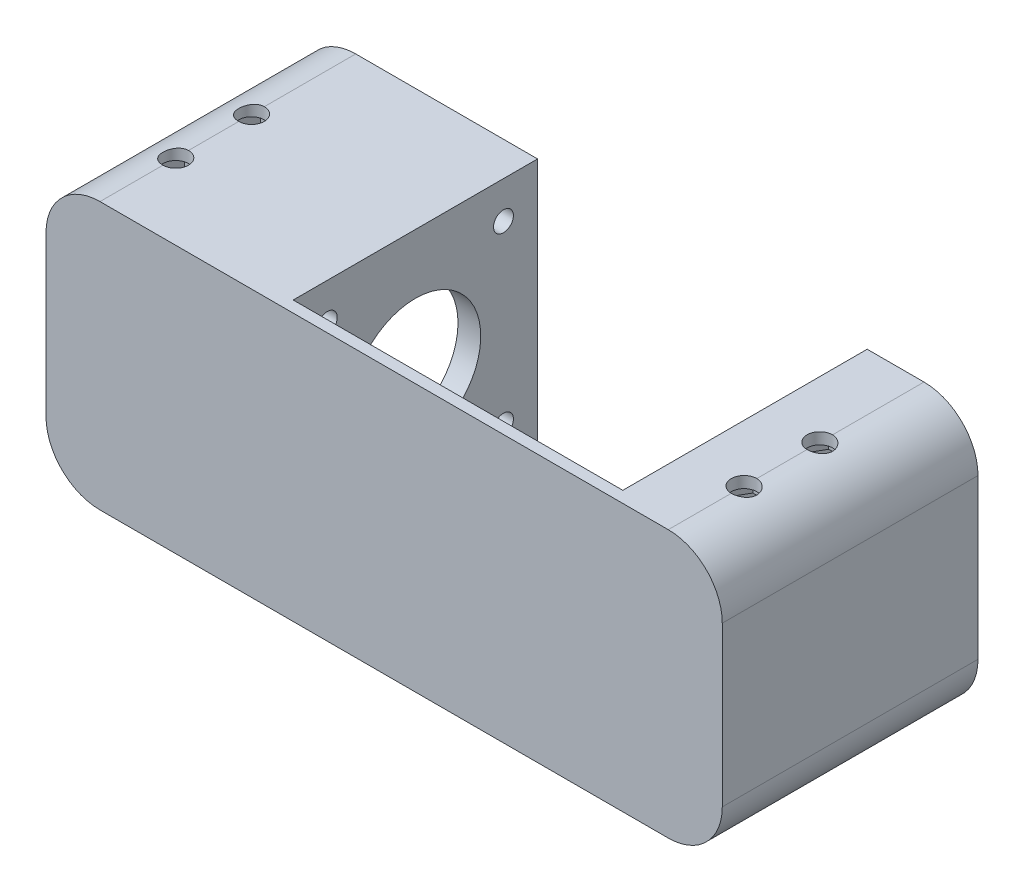
SolidWorks part; units mm, degrees
ref_plane "Front Plane" through (0, 0, 0) normal (0, 0, 1) x (1, 0, 0)
ref_plane "Top Plane" through (0, 0, 0) normal (0, 1, 0) x (1, 0, 0)
ref_plane "Right Plane" through (0, 0, 0) normal (1, 0, 0) x (0, 0, -1)
sketch "Sketch2" plane through (0, 0, 0) normal (0, 0, 1) x (1, 0, 0)
  line L0 (-18, 23.5) -> (-18, -19.5)
  line L1 (-50, -23.5) -> (50, -23.5)
  line L2 (-59.5, -14) -> (-59.5, 14)
  line L3 (-50, 23.5) -> (-18, 23.5)
  line L4 (59.5, -14) -> (59.5, 14)
  line L5 (-59.5, -23.5) -> (59.5, 23.5) construction
  line L6 (-59.5, 23.5) -> (59.5, -23.5) construction
  line L7 (-18, -19.5) -> (35, -19.5)
  line L8 (35, -19.5) -> (35, 23.5)
  line L9 (-50, 19.5) -> (-22, 19.5)
  line L10 (55.5, -14) -> (55.5, 14)
  line L11 (-50, -19.5) -> (-22, -19.5)
  line L12 (-55.5, -14) -> (-55.5, 14)
  line L13 (-22, 19.5) -> (-22, -19.5)
  line L14 (-22, -23.5) -> (39, -23.5)
  line L15 (39, -19.5) -> (39, 19.5)
  line L16 (39, 19.5) -> (50, 19.5)
  line L17 (-22, 23.5) -> (-22, -23.5) construction
  line L18 (35, 23.5) -> (50, 23.5)
  line L19 (-50, 19.5) -> (50, 19.5) construction
  line L20 (39, -19.5) -> (50, -19.5)
  line L21 (-50, 23.5) -> (50, 23.5) construction
  line L22 (39, -23.5) -> (39, 23.5) construction
  line L23 (-18, -19.5) -> (35, -19.5)
  line L24 (-50, -19.5) -> (50, -19.5) construction
  line L25 (-22, -19.5) -> (-22.1358, -19.362)
  arc A0 (-50, -23.5) -> (-59.5, -14) centre (-50, -14) cw
  arc A1 (50, -23.5) -> (59.5, -14) centre (50, -14) ccw
  arc A2 (50, 23.5) -> (59.5, 14) centre (50, 14) cw
  arc A3 (-59.5, 14) -> (-50, 23.5) centre (-50, 14) cw
  arc A4 (50, 19.5) -> (55.5, 14) centre (50, 14) cw
  arc A5 (50, -19.5) -> (55.5, -14) centre (50, -14) ccw
  arc A6 (-50, -19.5) -> (-55.5, -14) centre (-50, -14) cw
  arc A7 (-55.5, 14) -> (-50, 19.5) centre (-50, 14) cw
  point P0 (0, 0)
  dimension "D3" = 9.5
  dimension "D1" = 119
  dimension "D2" = 47
  dimension "D4" = 15
  dimension "D5" = 53
  dimension "D6" = 43
  dimension "D7" = 4
  dimension "D8" = 4
extrude "Boss-Extrude1" add sketch "Sketch2" along normal blind 43 contours A3 L2 A0 L1 A1 L4 A2 L18 L8 L7 L0 L3 A5 L20 L15 L16 A4 L10 L12 A7 L9 L13 L11 A6 region at (-19.2795, 2, 0)
sketch "Sketch3" plane through (-18, 0, 0) normal (1, 0, 0) x (0, 0, -1)
  line L0 (-21.5, 23.5) -> (-21.5, -20.5) construction
  line L1 (-43, 23.5) -> (0, 23.5) construction
  line L2 (-21.5, 1.5) -> (-37, 17) construction
  circle A0 centre (-21.5, 1.5) radius 11.5
  circle A1 centre (-37, 17) radius 1.75
  circle A2 centre (-37, -14) radius 1.75
  circle A3 centre (-6, -14) radius 1.75
  circle A4 centre (-6, 17) radius 1.75
  point P17 (-21.5, 1.5)
  dimension "D1" = 23
  dimension "D5" = 3.5
  dimension "D2" = 22
  dimension "D3" = 15.5
  dimension "D4" = 45
  dimension "D6" = 4
extrude "Cut-Extrude1" cut sketch "Sketch3" against normal blind 52
sketch "Sketch4" plane through (0, 0, 43) normal (0, 0, 1) x (1, 0, 0)
  line L0 (-18, 23.5) -> (35, 23.5)
  line L8 (-59.5, 14) -> (-59.5, -14)
  line L9 (-50, -23.5) -> (50, -23.5)
  line L10 (59.5, -14) -> (59.5, 14)
  line L11 (50, 23.5) -> (35, 23.5)
  line L12 (35, 23.5) -> (35, -19.5)
  line L13 (35, -19.5) -> (-18, -19.5)
  line L14 (-18, -19.5) -> (-18, 23.5)
  line L15 (-18, 23.5) -> (-50, 23.5)
  line L16 (-59.5, 14) -> (-59.5, -14)
  line L17 (-50, -23.5) -> (50, -23.5)
  line L18 (59.5, -14) -> (59.5, 14)
  line L19 (50, 23.5) -> (35, 23.5)
  line L23 (-18, 23.5) -> (-50, 23.5)
  arc A4 (-50, 23.5) -> (-59.5, 14) centre (-50, 14) ccw
  arc A5 (-59.5, -14) -> (-50, -23.5) centre (-50, -14) ccw
  arc A6 (50, -23.5) -> (59.5, -14) centre (50, -14) ccw
  arc A7 (59.5, 14) -> (50, 23.5) centre (50, 14) ccw
  arc A8 (-50, 23.5) -> (-59.5, 14) centre (-50, 14) ccw
  arc A9 (-59.5, -14) -> (-50, -23.5) centre (-50, -14) ccw
  arc A10 (50, -23.5) -> (59.5, -14) centre (50, -14) ccw
  arc A11 (59.5, 14) -> (50, 23.5) centre (50, 14) ccw
  dimension "D1" = 0
extrude "Boss-Extrude2" add sketch "Sketch4" along normal blind 2
sketch "Sketch5" plane through (0, 23.5, 0) normal (0, 1, 0) x (1, 0, 0)
  line L0 (-50, -45) -> (-50, -31.6667) construction
  line L1 (-50, -45) -> (-50, 0) construction
  line L2 (-50, -31.6667) -> (-50, -18.3333) construction
  line L3 (-50, -18.3333) -> (-50, -5) construction
  circle A0 centre (-50, -18.3333) radius 2.25
  circle A1 centre (-50, -31.6667) radius 2.25
  dimension "D2" = 4.5
  dimension "D1" = 40
extrude "Cut-Extrude2" cut sketch "Sketch5" against normal blind 50
sketch "Sketch6" plane through (0, -19.5, 0) normal (0, 1, 0) x (1, 0, 0)
  line L1 (-45.7276, -18.3333) -> (-47.8638, -14.6333)
  line L2 (-47.8638, -14.6333) -> (-52.1362, -14.6333)
  line L3 (-52.1362, -14.6333) -> (-54.2724, -18.3333)
  line L4 (-54.2724, -18.3333) -> (-52.1362, -22.0333)
  line L5 (-52.1362, -22.0333) -> (-47.8638, -22.0333)
  line L6 (-47.8638, -22.0333) -> (-45.7276, -18.3333)
  line L7 (-45.7276, -31.6667) -> (-47.8638, -27.9667)
  line L8 (-47.8638, -27.9667) -> (-52.1362, -27.9667)
  line L9 (-52.1362, -27.9667) -> (-54.2724, -31.6667)
  line L10 (-54.2724, -31.6667) -> (-52.1362, -35.3667)
  line L11 (-52.1362, -35.3667) -> (-47.8638, -35.3667)
  line L12 (-47.8638, -35.3667) -> (-45.7276, -31.6667)
  circle A0 centre (-50, -18.3333) radius 3.7 construction
  circle A1 centre (-50, -31.6667) radius 3.7 construction
  dimension "D1" = 7.4
extrude "Cut-Extrude3" cut sketch "Sketch6" against normal blind 2 and the other way blind 2
mirror "Mirror1" about plane through (0, 0, 0) normal (1, 0, 0) of "Cut-Extrude2"
mirror "Mirror2" about plane through (0, 0, 0) normal (0, 1, 0) of "Cut-Extrude3"
mirror "Mirror3" about plane through (0, 0, 0) normal (1, 0, 0) of "Mirror2"
sketch "Sketch7" plane through (-59.5, 0, 0) normal (-1, 0, 0) x (0, 0, 1)
  line L0 (14.6333, 19.5) -> (0, 19.5) construction
  circle A0 centre (6, 17) radius 2.5
  circle A1 centre (37, 17) radius 2.5
  circle A2 centre (37, -14) radius 2.5
  circle A3 centre (6, -14) radius 2.5
extrude "Cut-Extrude4" cut sketch "Sketch7" against normal blind 19
chamfer "Chamfer1" distance 5 angle 45 4 edges at (35, 23.5, 21.5) (39, 19.5, 21.5) (39, -19.5, 21.5) (35, -19.5, 21.5)
